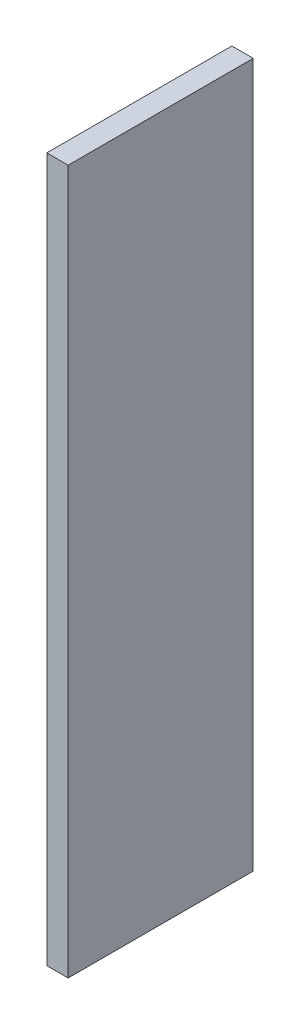
SolidWorks part; units mm, degrees
ref_plane "Front Plane" through (0, 0, 0) normal (0, 0, 1) x (1, 0, 0)
ref_plane "Top Plane" through (0, 0, 0) normal (0, 1, 0) x (1, 0, 0)
ref_plane "Right Plane" through (0, 0, 0) normal (1, 0, 0) x (0, 0, -1)
sketch "Sketch1" plane through (0, 0, 0) normal (1, 0, 0) x (0, 0, -1)
  line L1 (-65.1617, 81.9776) -> (99.9383, 81.9776)
  line L2 (-65.1617, 81.9776) -> (-65.1617, -545.9104)
  line L3 (-65.1617, -545.9104) -> (99.9383, -545.9104)
  line L4 (99.9383, 81.9776) -> (99.9383, -545.9104)
  line L5 (-65.1617, 81.9776) -> (99.9383, -545.9104) construction
  line L6 (-65.1617, -545.9104) -> (99.9383, 81.9776) construction
  point P0 (17.3883, -231.9664)
extrude "Boss-Extrude1" add sketch "Sketch1" along normal blind 19.05
